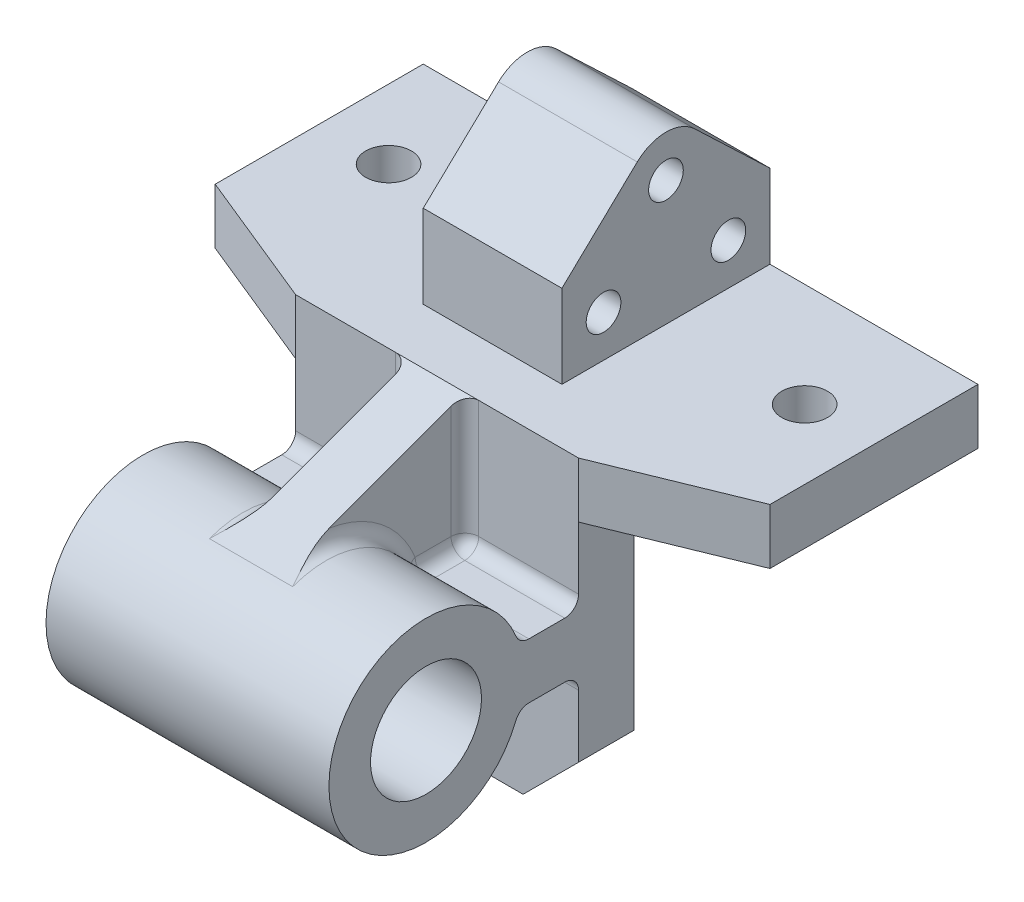
SolidWorks part; units mm, degrees
material "6061 合金"
ref_plane "前视基准面" through (0, 0, 0) normal (0, 0, 1) x (1, 0, 0)
ref_plane "上视基准面" through (0, 0, 0) normal (0, 1, 0) x (1, 0, 0)
ref_plane "右视基准面" through (0, 0, 0) normal (1, 0, 0) x (0, 0, -1)
sketch "草图2" plane through (0, 0, 0) normal (1, 0, 0) x (0, 0, -1)
  line L0 (-2.4145, -6.5704) -> (11, -11.5)
  line L2 (15, -11.5) -> (15, 7.5)
  line L3 (15, -11.5) -> (11, -11.5)
  line L5 (-2.4145, 6.5704) -> (11, 11.5)
  line L12 (30, 7.5) -> (30, 11.5)
  line L13 (15, 7.5) -> (30, 7.5)
  line L14 (11, 11.5) -> (30, 11.5)
  line L15 (11, 11.5) -> (11, -11.5) construction
  arc A1 (-2.4145, 6.5704) -> (-2.4145, -6.5704) centre (0, 0) ccw
  circle A6 centre (0, 0) radius 4
  dimension "D1" = 7
  dimension "D2" = 4
  dimension "D5" = 8
  dimension "D7" = 4
  dimension "D3" = 15
  dimension "D6" = 11.5
  dimension "D4" = 7.5
  dimension "D8" = 15
extrude "凸台-拉伸1" add sketch "草图2" along normal mid plane 20.4
sketch "草图9" plane through (0, 0, 0) normal (1, 0, 0) x (0, 0, -1)
  line L0 (-2.4145, -6.5704) -> (11, -11.5) construction
  line L1 (11, 11.5) -> (-2.4145, 6.5704) construction
  line L2 (-2.4145, -6.5704) -> (11, -11.5)
  line L5 (11, 11.5) -> (-2.4145, 6.5704)
  line L6 (11, -11.5) -> (11, -2)
  line L7 (6.7082, 2) -> (11, 2)
  line L8 (0, 0) -> (10, 0) construction
  line L9 (6.7082, -2) -> (11, -2)
  line L10 (11, 2) -> (11, 11.5)
  arc A0 (-2.4145, 6.5704) -> (-2.4145, -6.5704) centre (0, 0) ccw construction
  arc A1 (-2.4145, -6.5704) -> (6.7082, -2) centre (0, 0) ccw
  arc A2 (6.7082, 2) -> (-2.4145, 6.5704) centre (0, 0) ccw
  dimension "D1" = 4
extrude "切除-拉伸1" cut sketch "草图9" along normal through all from offset 2
sketch "草图10" plane through (10.2, 0, 0) normal (1, 0, 0) x (0, 0, -1)
  line L0 (30, 7.5) -> (30, 11.5) construction
  line L1 (30, 11.5) -> (11, 11.5) construction
  line L2 (15, 7.5) -> (30, 7.5) construction
  line L3 (15, -11.5) -> (15, 7.5) construction
  line L4 (11, -11.5) -> (15, -11.5) construction
  line L5 (11, 2) -> (11, 11.5) construction
  line L6 (30, 7.5) -> (30, 11.5)
  line L7 (30, 11.5) -> (11, 11.5)
  line L8 (15, 7.5) -> (30, 7.5)
  line L9 (15, -11.5) -> (15, 7.5)
  line L10 (11, -11.5) -> (15, -11.5)
  line L11 (11, -11.5) -> (11, 11.5)
extrude "凸台-拉伸2" [suppressed] add sketch "草图10" along normal blind 4.5
mirror "镜向1" about plane through (0, 0, 0) normal (1, 0, 0) of "切除-拉伸1"
hole_wizard "M3 螺纹孔1" positions "草图11" profile "草图12" tap size "M3" standard "GB" end condition up to next
sketch "草图11" plane through (0, 0, -15) normal (0, 0, -1) x (-1, 0, 0)
  line L0 (-2, 2) -> (2, -2) construction
  point P0 (0, 0)
sketch "草图12" plane through (0, 0, -15) normal (1, 0, 0) x (0, 1, 0)
  line L0 (0, 0) -> (0, 11)
  line L1 (0, 11) -> (1.25, 11)
  line L2 (1.25, 11) -> (1.25, 0)
  line L5 (1.25, 0) -> (0, 0)
  line L11 (0, -6.35) -> (0, 107.95) construction
  dimension "通孔螺纹孔钻头直径" = 2.5
  dimension "通孔螺纹孔钻头深度" = 11
cosmetic thread "孔螺蚊线3" parameters "D2"=3
sketch "草图13" plane through (0, 11.5, 0) normal (0, 1, 0) x (1, 0, 0)
  line L0 (10.2, 30) -> (-10.2, 30) construction
  line L1 (20, 30) -> (-20, 30)
  line L2 (2, 11) -> (-2, 11) construction
  line L4 (-20, 30) -> (-20, 15)
  line L6 (0, -19.25) -> (0, 19.25) construction
  line L8 (20, 30) -> (20, 15)
  line L11 (-10.2, 11) -> (-20, 15)
  line L13 (10.2, 11) -> (-10.2, 11)
  line L15 (10.2, 11) -> (20, 15)
  dimension "D1" = 15
  dimension "D2" = 40
extrude "凸台-拉伸3" add sketch "草图13" against normal up to surface (4 mm away) up to face at (0, 7.5, -22.5)
hole_wizard "M4 螺纹孔2" positions "草图7" profile "草图8" tap size "M4" standard "GB" end condition through all
sketch "草图7" plane through (0, 11.5, 0) normal (0, 1, 0) x (-1, 0, 0)
  line L0 (-15, -22.5) -> (15, -22.5) construction
  line L5 (0, 19.25) -> (0, -19.25) construction
  line L6 (-20, -30) -> (20, -30) construction
  point P0 (-15, -22.5)
  point P23 (15, -22.5)
  dimension "D1" = 30
  dimension "D2" = 7.5
sketch "草图8" plane through (15, 11.5, -22.5) normal (1, 0, 0) x (0, 0, 1)
  line L0 (0, 0) -> (0, 23)
  line L1 (0, 23) -> (1.65, 23)
  line L2 (1.65, 23) -> (1.65, 0)
  line L5 (1.65, 0) -> (0, 0)
  line L11 (0, -6.35) -> (0, 107.95) construction
  dimension "通孔螺纹孔钻头直径" = 3.3
  dimension "通孔螺纹孔钻头深度" = 23
cosmetic thread "孔螺蚊线1" parameters "D2"=4
cosmetic thread "孔螺蚊线2" parameters "D2"=4
chamfer "倒角1" distance 4 angle 45 2 edges at (10.2, -11.5, -13) (-10.2, -11.5, -13)
sketch "草图14" plane through (0, 0, 0) normal (1, 0, 0) x (0, 0, -1)
  line L0 (15, 17.5) -> (20.431, 22.6724)
  line L1 (24.569, 22.6724) -> (30, 17.5)
  line L2 (30, 11.5) -> (15, 11.5)
  line L3 (22.5, 20.5) -> (22.5, 11.5) construction
  line L4 (15, 11.5) -> (15, 17.5)
  line L5 (30, 11.5) -> (30, 17.5)
  line L6 (15, -7.5) -> (15, 7.5) construction
  arc A0 (20.431, 22.6724) -> (24.569, 22.6724) centre (22.5, 20.5) cw
  circle A1 centre (22.5, 20.5) radius 1.5 construction
  circle A2 centre (18, 14.5) radius 1.5 construction
  circle A4 centre (27, 14.5) radius 1.5 construction
  dimension "D1" = 3
  dimension "D2" = 3
  dimension "D3" = 3
  dimension "D6" = 9
  dimension "D4" = 6
  dimension "D5" = 9
extrude "凸台-拉伸4" add sketch "草图14" along normal mid plane 10
hole_wizard "M3 螺纹孔2" positions "草图15" profile "草图16" tap size "M3" standard "GB" end condition up to next
sketch "草图15" plane through (5, 0, 0) normal (1, 0, 0) x (0, 0, -1)
  point P0 (22.5, 20.5)
  point P2 (18, 14.5)
  point P4 (27, 14.5)
sketch "草图16" plane through (5, 20.5, -22.5) normal (0, 1, 0) x (0, 0, -1)
  line L0 (0, 0) -> (0, 10)
  line L1 (0, 10) -> (1.25, 10)
  line L2 (1.25, 10) -> (1.25, 0)
  line L5 (1.25, 0) -> (0, 0)
  line L11 (0, -6.35) -> (0, 107.95) construction
  dimension "通孔螺纹孔钻头直径" = 2.5
  dimension "通孔螺纹孔钻头深度" = 10
cosmetic thread "孔螺蚊线4" parameters "D2"=3
cosmetic thread "孔螺蚊线5" parameters "D2"=3
cosmetic thread "孔螺蚊线6" parameters "D2"=3
fillet "圆角1" radius 1 20 edges at (-2, -6.75, -11) (-2, -2, -8.8541) (2, -6.75, -11) (2, -2, -8.8541) (-2, 2, -8.8541) (2, 2, -8.8541) (2, 6.75, -11) (-2, 6.75, -11) (-6.1, -2, -6.7082) (-6.1, -2, -11) (-6.1, 2, -6.7082) (-6.1, 2, -11) (6.1, -2, -11) (6.1, -2, -6.7082) (6.1, 2, -6.7082) (6.1, 2, -11) (2, 6.2585, -3.1355) (-2, 6.2585, -3.1355) (-2, -6.2585, -3.1355) (2, -6.2585, -3.1355)
